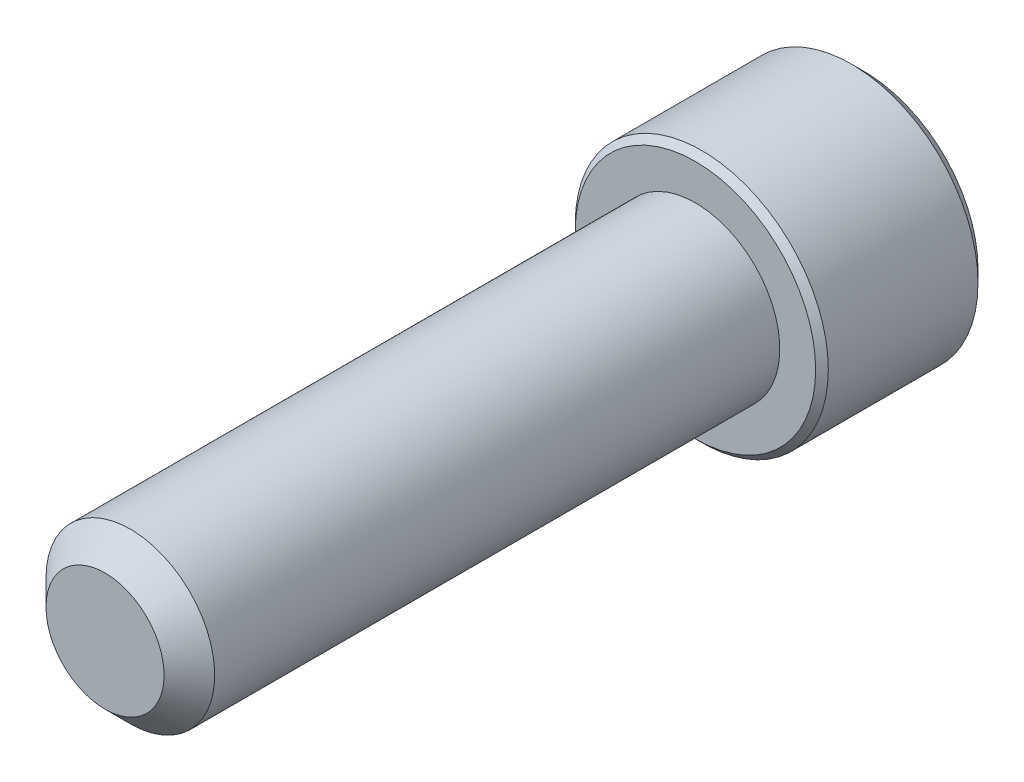
SolidWorks part; units mm, degrees
ref_plane "Front Plane" through (0, 0, 0) normal (0, 0, 1) x (1, 0, 0)
ref_plane "Top Plane" through (0, 0, 0) normal (0, 1, 0) x (1, 0, 0)
ref_plane "Right Plane" through (0, 0, 0) normal (1, 0, 0) x (0, 0, -1)
sketch "Sketch0" plane through (0, 0, 0) normal (1, 0, 0) x (0, 0, -1)
  line L0 (0, 0) -> (22.225, 0) construction
  point P2 (28.575, 0)
  point P4 (0, 0)
  dimension "D1" = 22.225
  dimension "D2" = 6.35
  dimension "Min Thread" = 0
sketch "Sketch1" plane through (0, 0, 0) normal (0, 0, 1) x (1, 0, 0)
  circle A0 centre (0, 0) radius 3.175
  dimension "OD" = 6.35
extrude "Extrude1" add sketch "Sketch1" against normal blind 22.225
sketch "Sketch2" plane through (0, 0, 0) normal (0, 0, 1) x (1, 0, 0)
  circle A0 centre (0, 0) radius 3.175 construction
  circle A1 centre (0, 0) radius 3.175
curve "Helix/Spiral1" pitch 1.27 height 23.495 turns 18.5 parameters "pitch"=1.27
chamfer "Chamfer3" distance 0.9525 angle 45 1 edges at (3.175, 0, 0)
sketch "Sketch3" plane through (0, 0, 0) normal (1, 0, 0) x (0, 0, -1)
  line L0 (-1.1113, 3.175) -> (-0.635, 2.3501)
  line L1 (-0.635, 2.3501) -> (-0.4763, 2.3501)
  line L2 (-0.4763, 2.3501) -> (0, 3.175)
  line L3 (-1.1113, 3.175) -> (0, 3.175)
  line L4 (-0.5556, 3.175) -> (-0.5556, 2.3501) construction
  line L5 (-0.8731, 2.7626) -> (-0.2381, 2.7626) construction
  line L6 (0, 3.175) -> (0, -3.175) construction
  dimension "D1" = 0.1588
  dimension "D2" = 0.635
  dimension "D3" = 60
sweep "Cut-Sweep1" [suppressed] cut profiles "Sketch3" path "Helix/Spiral1"
sketch "Sketch5" [suppressed] plane through (0, 0, 0) normal (1, 0, 0) x (0, 0, -1)
  line L0 (22.225, -2.2654) -> (22.225, 2.3728) construction
  line L1 (22.225, 3.175) -> (0, 3.175)
  line L2 (22.225, 3.175) -> (22.225, 0)
  line L3 (22.225, 0) -> (-1.1556, 0)
  line L4 (0, 0) -> (22.225, 0) construction
  line L5 (0, 3.175) -> (-1.1556, 0)
  line L6 (0, 0) -> (24.765, 0) construction
  dimension "D1" = 70
  dimension "D3" = 2.54
revolve "partially thread" [suppressed] add sketch "Sketch5" angle 360 about L6
sketch "Sketch6" plane through (0, 0, -22.225) normal (0, 0, -1) x (-1, 0, 0)
  circle A0 centre (0, 0) radius 4.7625
  dimension "head dia" = 9.525
extrude "Extrude2" add sketch "Sketch6" along normal blind 6.35
sketch "Sketch7" plane through (0, 0, -28.575) normal (0, 0, -1) x (-1, 0, 0)
  line L1 (0, 2.7496) -> (-2.3813, 1.3748)
  line L2 (-2.3813, 1.3748) -> (-2.3813, -1.3748)
  line L3 (-2.3813, -1.3748) -> (0, -2.7496)
  line L4 (0, -2.7496) -> (2.3813, -1.3748)
  line L5 (2.3813, -1.3748) -> (2.3813, 1.3748)
  line L6 (2.3813, 1.3748) -> (0, 2.7496)
  circle A0 centre (0, 0) radius 2.3813 construction
  dimension "hex dia" = 4.7625
extrude "Cut-Extrude1" cut sketch "Sketch7" against normal blind 3.5719
sketch "Sketch8" plane through (0, 0, -28.575) normal (0, 0, -1) x (-1, 0, 0)
  circle A0 centre (0, 0) radius 2.7496
extrude "Cut-Extrude2" cut sketch "Sketch8" against normal through all draft 45
chamfer "Chamfer1" distance 0.4763 angle 45 1 edges at (-4.7625, 0, -28.575)
chamfer "Chamfer2" distance 0.2381 angle 45 1 edges at (-4.7625, 0, -22.225)
sketch "Sketch9" plane through (0, 0, 0) normal (1, 0, 0) x (0, 0, -1)
  line L0 (0, 3.175) -> (0, -3.175) construction
  line L1 (3.175, 3.175) -> (3.175, -3.175) construction
  line L2 (28.575, 4.7625) -> (28.575, -4.7625) construction
  line L3 (22.225, 4.7625) -> (22.225, -4.7625) construction
  line L4 (22.225, 4.5244) -> (22.225, -4.5244) construction
  line L5 (28.575, -4.2862) -> (28.575, 4.2862) construction
  line L6 (22.225, -4.7625) -> (22.225, 4.7625) construction
  line L7 (0, 2.2225) -> (0, -2.2225) construction
  line L8 (-1.1113, 3.175) -> (0, 3.175) construction
  line L9 (3.175, 0) -> (0, 0) construction
  dimension "D1" = 3.175
equation "\"D3@Helix/Spiral1\" = \"screw length@Extrude1\"+\"pitch@Helix/Spiral1\""
equation "\"D1@Sketch3\" = \"pitch@Helix/Spiral1\"*.125"
equation "\"D2@Sketch3\" = \"pitch@Helix/Spiral1\"*.5"
equation "\"D1@Cut-Extrude1\" = \"hex dia@Sketch7\"*.75"
equation "\"D1@Chamfer1\" = \"head dia@Sketch6\"*.05"
equation "\"D1@Sketch9\" = \"pitch@Helix/Spiral1\"*2.50"
equation "\"D1@Chamfer2\" = \"D1@Chamfer1\"/2"
equation "\"D1@Chamfer3\" = \"pitch@Helix/Spiral1\"*.750"
equation "\"D1@Sketch0\" = \"screw length@Extrude1\""
equation "\"D2@Sketch0\" = \"head depth@Extrude2\""
